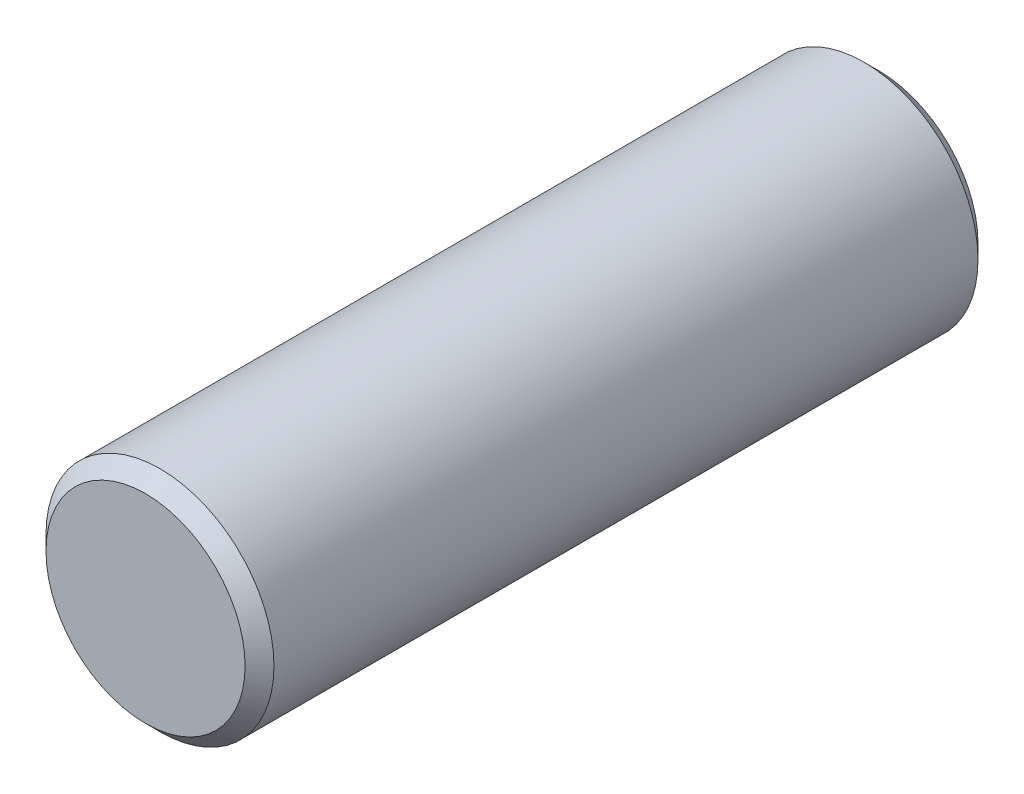
SolidWorks part; units mm, degrees
ref_plane "Front Plane" through (0, 0, 0) normal (0, 0, 1) x (1, 0, 0)
ref_plane "Top Plane" through (0, 0, 0) normal (0, 1, 0) x (1, 0, 0)
ref_plane "Right Plane" through (0, 0, 0) normal (1, 0, 0) x (0, 0, -1)
sketch "Sketch1" plane through (0, 0, 0) normal (0, 0, 1) x (1, 0, 0)
  circle A0 centre (0, 0) radius 3.95
  dimension "D1" = 7.9
extrude "Boss-Extrude1" add sketch "Sketch1" along normal mid plane 25.4
chamfer "Chamfer1" distance 0.5 angle 45 2 edges at (3.95, 0, -12.7) (3.95, 0, 12.7)
